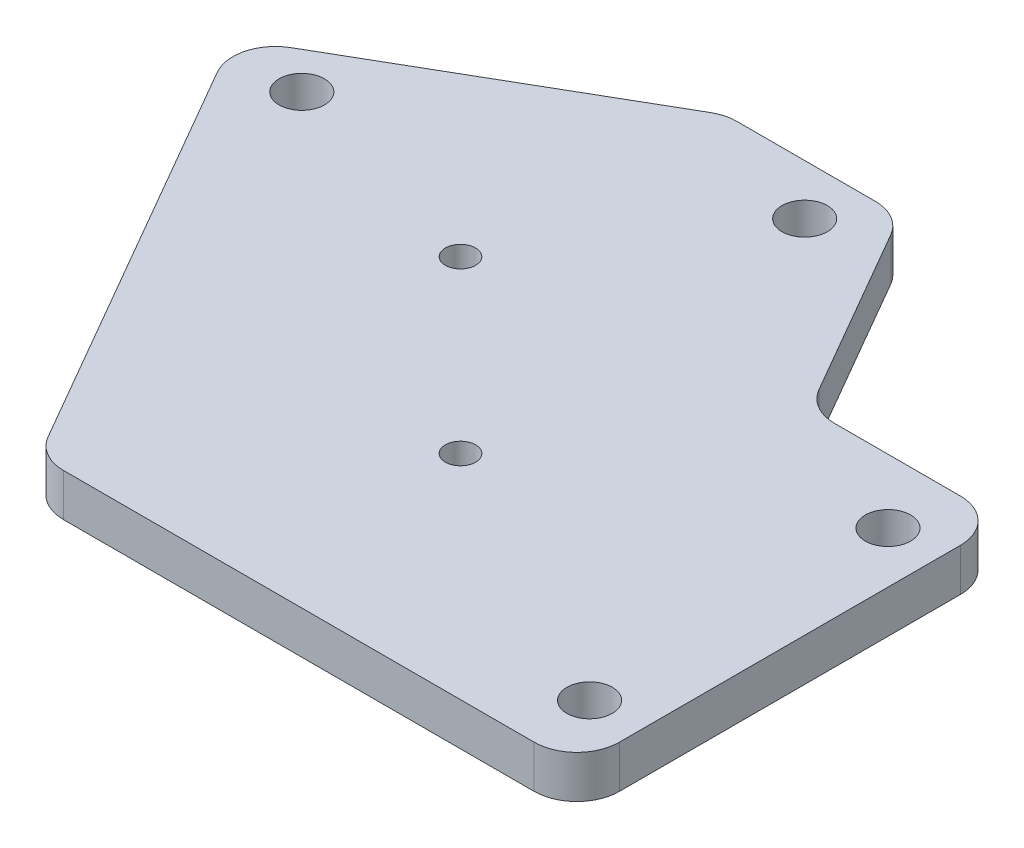
SolidWorks part; units mm, degrees
ref_plane "Front Plane" through (0, 0, 0) normal (0, 0, 1) x (1, 0, 0)
ref_plane "Top Plane" through (0, 0, 0) normal (0, 1, 0) x (1, 0, 0)
ref_plane "Right Plane" through (0, 0, 0) normal (1, 0, 0) x (0, 0, -1)
sketch "Sketch1" plane through (0, 0, 0) normal (0, 1, 0) x (1, 0, 0)
  line L0 (0, 295.91) -> (0, -295.91) construction
  line L1 (-52.8096, -159.9) -> (76.5275, -159.9) construction
  line L2 (-185.3, -83.4066) -> (-52.8096, -159.9) construction
  line L3 (-26.867, 159.9) -> (-52.8096, 159.9)
  line L4 (-52.8096, 159.9) -> (-185.3, 83.4066) construction
  line L5 (76.5275, 159.9) -> (-52.8096, 159.9) construction
  line L6 (0, 159.9) -> (0, -159.9) construction
  line L7 (-52.8096, -159.9) -> (0, -159.9) construction
  line L8 (-185.3, -83.4066) -> (-52.8096, -159.9) construction
  line L10 (-52.8096, 159.9) -> (-185.3, 83.4066) construction
  line L11 (0, 159.9) -> (-52.8096, 159.9) construction
  line L12 (-52.8096, 159.9) -> (-99.3438, 133.0335)
  line L13 (-99.3438, 133.0335) -> (-59.9018, 64.7181)
  line L14 (-59.9018, 64.7181) -> (20.2, 64.7181)
  line L17 (20.2, 128.2181) -> (-8.5754, 128.2181)
  line L18 (-8.5754, 128.2181) -> (-26.867, 159.9)
  line L19 (-41.571, 109.1681) -> (-8.5754, 128.2181) construction
  line L20 (-41.571, 109.1681) -> (-74.5665, 90.1181) construction
  line L21 (-41.571, 109.1681) -> (-41.571, 64.7181) construction
  line L24 (20.2, 128.2181) -> (20.2, 64.7181) construction
  line L25 (20.2, 7.5) -> (20.2, 144.9) construction
  line L26 (20.2, 128.2181) -> (20.2, 64.7181)
  circle A0 centre (-41.571, 109.1681) radius 2.54 construction
  circle A1 centre (-41.571, 109.1681) radius 2.54 construction
  dimension "D1" = 38.1
  dimension "D2" = 44.45
extrude "Boss-Extrude1" add sketch "Sketch1" against normal blind 6.35
fillet "Fillet1" radius 6.35 7 edges at (-8.5754, -3.175, -128.2181) (-99.3438, -3.175, -133.0335) (-52.8096, -3.175, -159.9) (-26.867, -3.175, -159.9) (20.2, -3.175, -128.2181) (20.2, -3.175, -64.7181) (-59.9018, -3.175, -64.7181)
hole_wizard "1/4 Clearance Hole2" positions "Sketch4" profile "Sketch5" hole size "1/4" standard "ANSI Inch" end condition through all
sketch "Sketch4" plane through (0, -6.35, 0) normal (0, -1, 0) x (-1, 0, 0)
  line L14 (-12.58, 165.1) -> (-12.58, 139.7) construction
  line L15 (-76.7545, 165.1) -> (54.203, 165.1) construction
  line L16 (-75.6455, 139.7) -> (47.397, 139.7) construction
  line L18 (-12.58, 152.4) -> (33.5353, 152.4) construction
  line L20 (87.3449, 131.3008) -> (93.6949, 142.2993) construction
  line L21 (54.203, 165.1) -> (190.5, 86.4089) construction
  line L22 (10.4085, 131.3931) -> (25.0339, 156.725) construction
  line L23 (54.203, 165.1) -> (190.5, 86.4089) construction
  line L24 (96.1688, 127.5342) -> (61.7349, 67.8931) construction
  line L26 (-12.58, 152.4) -> (-12.58, 64.7181) construction
  line L28 (-20.2, 71.0681) -> (-20.2, 121.8681) construction
  line L29 (56.2357, 64.7181) -> (-13.85, 64.7181) construction
  line L30 (-13.85, 128.2181) -> (4.9092, 128.2181) construction
  point P2 (87.3449, 131.3008)
  point P53 (33.5353, 152.4)
  point P83 (-12.58, 74.2431)
  point P85 (-12.58, 118.6931)
  dimension "D1" = 9.525
  dimension "D2" = 12.7
  dimension "D3" = 9.525
  dimension "D4" = 9.525
  dimension "D5" = 7.62
  dimension "D6" = 9.525
sketch "Sketch5" plane through (-87.3449, -6.35, -131.3008) normal (1, 0, 0) x (0, 0, -1)
  line L0 (0, 0) -> (0, 6.35)
  line L1 (0, 6.35) -> (3.3782, 6.35)
  line L2 (3.3782, 6.35) -> (3.3782, 0)
  line L5 (3.3782, 0) -> (0, 0)
  line L11 (0, -6.35) -> (0, 107.95) construction
  dimension "Thru Hole Dia." = 6.7564
  dimension "Thru Hole Depth" = 6.35
hole_wizard "#8 Clearance Hole1" positions "Sketch8" profile "Sketch9" hole size "#8" standard "ANSI Inch" end condition through all
sketch "Sketch8" plane through (0, 0, 0) normal (0, 1, 0) x (1, 0, 0)
  circle A1 centre (-54.269, 121.8662) radius 2.159 construction
  circle A2 centre (-28.8729, 96.47) radius 2.159 construction
  circle A3 centre (-54.269, 121.8662) radius 2.159
  circle A4 centre (-28.8729, 96.47) radius 2.159
  point P6 (-54.269, 121.8662)
  point P8 (-28.8729, 96.47)
sketch "Sketch9" plane through (-54.269, 0, -121.8662) normal (1, 0, 0) x (0, 0, 1)
  line L0 (0, 0) -> (0, 6.35)
  line L1 (0, 6.35) -> (2.2479, 6.35)
  line L2 (2.2479, 6.35) -> (2.2479, 0)
  line L5 (2.2479, 0) -> (0, 0)
  line L11 (0, -6.35) -> (0, 107.95) construction
  dimension "Thru Hole Dia." = 4.4958
  dimension "Thru Hole Depth" = 6.35
